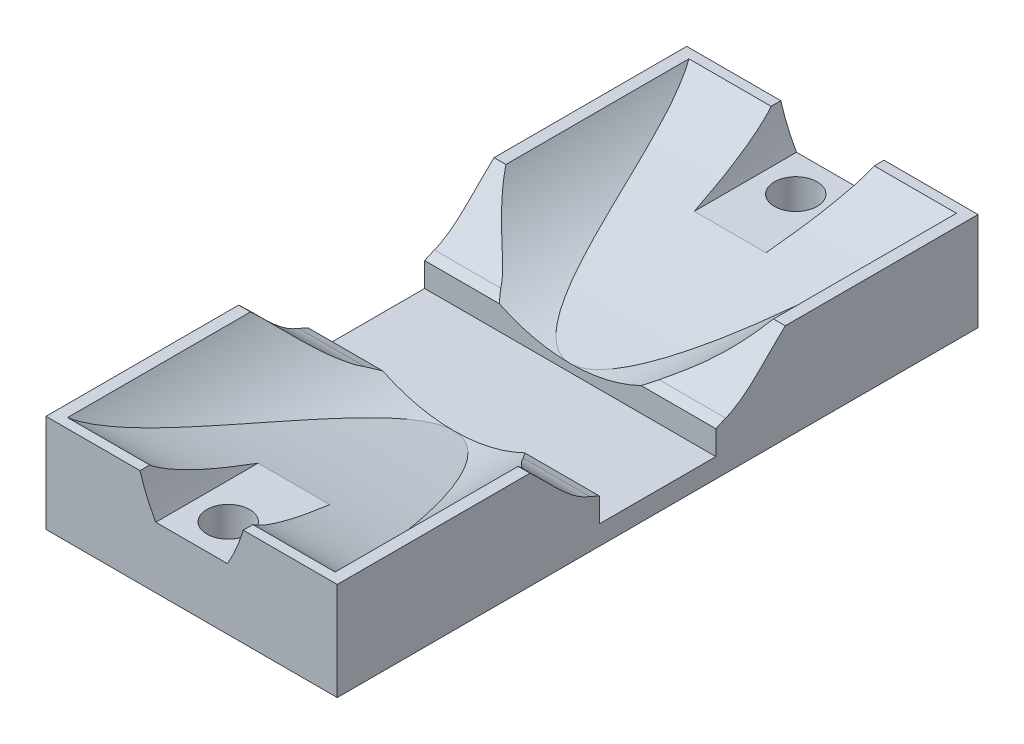
SolidWorks part; units mm, degrees
ref_plane "Front Plane" through (0, 0, 0) normal (0, 0, 1) x (1, 0, 0)
ref_plane "Top Plane" through (0, 0, 0) normal (0, 1, 0) x (1, 0, 0)
ref_plane "Right Plane" through (0, 0, 0) normal (1, 0, 0) x (0, 0, -1)
sketch "Sketch1" plane through (0, 0, 0) normal (0, 1, 0) x (1, 0, 0)
  line L0 (-185, -65) -> (5, -65)
  line L1 (-185, 135) -> (185, 135)
  line L2 (-185, 135) -> (-185, -65)
  line L4 (185, 135) -> (185, -135)
  line L8 (91.1823, -135) -> (185, -135)
  arc A0 (5, -65) -> (91.1823, -135) centre (5, -153.0528) cw
  point P0 (0, 0)
extrude "Boss-Extrude1" add sketch "Sketch1" along normal blind 15.0459
sketch "Sketch2" plane through (0, 15.0459, 0) normal (0, 1, 0) x (1, 0, 0)
  line L0 (-175, -35) -> (-175, 30)
  line L1 (-175, -35) -> (-142.5, -35)
  line L2 (-175, 125) -> (-142.5, 125)
  line L3 (-95, -35) -> (-95, 30)
  line L12 (-185, 135) -> (-185, -65) construction
  line L13 (-185, 135) -> (-142.5, 135)
  line L14 (-85, -45) -> (-85, 30)
  line L15 (-185, -45) -> (-142.5, -45)
  line L16 (-185, -45) -> (-185, 30)
  line L17 (-135, 196.4351) -> (-135, -108.7974) construction
  line L18 (-142.5, 135) -> (-142.5, 125)
  line L19 (-127.5, 135) -> (-127.5, 125)
  line L20 (-127.5, 135) -> (-85, 135)
  line L21 (-185, 135) -> (-85, 135) construction
  line L22 (-127.5, 125) -> (-95, 125)
  line L23 (-175, 125) -> (-95, 125) construction
  line L24 (-208.7616, 45) -> (-62.2564, 45) construction
  line L25 (-127.5, -45) -> (-127.5, -35)
  line L26 (-142.5, -45) -> (-142.5, -35)
  line L27 (-127.5, -35) -> (-95, -35)
  line L28 (-175, -35) -> (-95, -35) construction
  line L29 (-127.5, -45) -> (-85, -45)
  line L30 (-185, -45) -> (-85, -45) construction
  line L31 (185, 135) -> (-185, 135) construction
  line L32 (-175, 60) -> (-185, 60)
  line L33 (-175, 30) -> (-185, 30)
  line L34 (-95, 60) -> (-85, 60)
  line L35 (-95, 30) -> (-85, 30)
  line L36 (-175, 60) -> (-175, 125)
  line L37 (-175, -35) -> (-175, 125) construction
  line L38 (-185, 60) -> (-185, 135)
  line L39 (-185, -45) -> (-185, 135) construction
  line L40 (-85, 60) -> (-85, 135)
  line L41 (-85, -45) -> (-85, 135) construction
  line L42 (-95, 60) -> (-95, 125)
  line L43 (-95, -35) -> (-95, 125) construction
  point P14 (-135, 135.0621)
  point P18 (-175, 45)
  dimension "D1" = 160
  dimension "D2" = 80
  dimension "D3" = 10
  dimension "D4" = 7.5
  dimension "D5" = 50
  dimension "D6" = 30
  dimension "D7" = 15
extrude "Boss-Extrude2" add sketch "Sketch2" along normal blind 30
sketch "Sketch3" plane through (0, 0, -125) normal (0, 0, 1) x (1, 0, 0)
  line L0 (-127.5, 15.0459) -> (-142.5, 15.0459) construction
  line L4 (-142.5, 15.0459) -> (-142.5, 13.7784)
  line L7 (-142.5, 13.7784) -> (-127.5, 13.7784)
  line L8 (-175, 15.0459) -> (-142.5, 15.0459)
  line L9 (-142.5, 15.0459) -> (-142.5, 45.0459)
  line L10 (-142.5, 45.0459) -> (-175, 45.0459)
  line L11 (-175, 45.0459) -> (-175, 15.0459)
  line L12 (-175, 15.0459) -> (-142.5, 15.0459)
  line L14 (-142.5, 45.0459) -> (-175, 45.0459)
  line L15 (-175, 45.0459) -> (-175, 15.0459)
  line L16 (-127.5, 15.0459) -> (-95, 15.0459)
  line L17 (-95, 15.0459) -> (-95, 45.0459)
  line L18 (-95, 45.0459) -> (-127.5, 45.0459)
  line L19 (-127.5, 45.0459) -> (-127.5, 15.0459)
  line L20 (-127.5, 15.0459) -> (-95, 15.0459)
  line L21 (-95, 15.0459) -> (-95, 45.0459)
  line L22 (-95, 45.0459) -> (-127.5, 45.0459)
  line L24 (-127.5, 13.7784) -> (-127.5, 15.0459)
  line L27 (-142.5, 15.0459) -> (-142.5, 45.0459)
  line L28 (-127.5, 45.0459) -> (-127.5, 15.0459)
  arc A0 (-175, 45.0459) -> (-138.7313, 15.2133) centre (-135, 56.7125) ccw
  arc A1 (-131.2687, 15.2133) -> (-95, 45.0459) centre (-135, 56.7125) ccw
  arc A2 (-138.7313, 15.2133) -> (-131.2687, 15.2133) centre (-135, 56.7125) ccw
  point P0 (-135, 15.0459)
  line M9 (-175, 15.0459) -> (-142.5, 15.0459)
  line M10 (-142.5, 15.0459) -> (-142.5, 45.0459)
  line M12 (-175, 45.0459) -> (-175, 15.0459)
  dimension "D1" = 0
  dimension "D2" = 0
extrude "Boss-Extrude3" add sketch "Sketch3" along normal up to surface (160 mm away) contours A0 M12 M9 M10 | A0 L20 L21 | A0 M10 region at (-135, 14.539, -125) region at (-165.9764, 23.0143, -125) region at (-104.0236, 23.0143, -125) up to face at (-158.75, 30.0459, 35)
sketch "Sketch5" plane through (-185, 0, 0) normal (-1, 0, 0) x (0, 0, 1)
  line L0 (-60, 45.0459) -> (-30, 45.0459)
  line L10 (-135, 0) -> (65, 0)
  line L11 (65, 0) -> (65, 15.0459)
  line L12 (65, 15.0459) -> (45, 15.0459)
  line L13 (45, 15.0459) -> (45, 45.0459)
  line L14 (45, 45.0459) -> (-30, 45.0459)
  line L15 (-30, 45.0459) -> (-30, 15.0459)
  line L16 (-30, 15.0459) -> (-60, 15.0459)
  line L17 (-60, 15.0459) -> (-60, 45.0459)
  line L18 (-60, 45.0459) -> (-135, 45.0459)
  line L19 (-135, 45.0459) -> (-135, 0)
  line L25 (-30, 45.0459) -> (-30, 15.0459)
  line L26 (-30, 15.0459) -> (-60, 15.0459)
  line L27 (-60, 15.0459) -> (-60, 45.0459)
  dimension "D1" = 0
extrude "Cut-Extrude1" cut sketch "Sketch5" against normal through all both and the other way through all
sketch "Sketch6" plane through (0, 15.0459, 0) normal (0, 1, 0) x (1, 0, 0)
  line L0 (-85, 60) -> (-85, 30)
  line L1 (-200, -45) -> (-127.5, -45)
  line L18 (-85, 135) -> (-85, 60)
  line L19 (-85, 60) -> (-135, 60)
  line L21 (-185, 60) -> (-185, 30)
  line L22 (-185, 30) -> (-135, 30)
  line L24 (-85, 30) -> (-85, -45)
  line L25 (-85, 30) -> (-85, -45)
  line L26 (-85, -45) -> (-127.5, -45)
  line L27 (-85, -45) -> (-127.5, -45)
  line L28 (-135, 60) -> (-185, 60)
  line L29 (-135, 60) -> (-185, 60)
  line L30 (-135, 30) -> (-85, 30)
  line L31 (-185, -45) -> (-185, -65)
  line L32 (-185, -65) -> (5, -65)
  line L33 (91.1823, -135) -> (185, -135)
  line L34 (185, -135) -> (185, 135)
  line L35 (185, 135) -> (-85, 135)
  line L36 (-85, 135) -> (-85, 60)
  line L37 (-85, 60) -> (-135, 60)
  line L39 (-185, 60) -> (-185, 30)
  line L40 (-185, 30) -> (-135, 30)
  line L49 (-185, -45) -> (-185, -65)
  line L50 (-185, -65) -> (5, -65)
  line L51 (91.1823, -135) -> (185, -135)
  line L52 (185, -135) -> (185, 135)
  line L53 (185, 135) -> (-85, 135)
  line L54 (-135, 30) -> (-85, 30)
  line L55 (-127.5, -45) -> (-127.5, -35)
  line L56 (-127.5, -45) -> (-127.5, -35)
  line L57 (-127.5, -35) -> (-135, -35)
  line L58 (-127.5, -35) -> (-135, -35)
  line L59 (-135, -35) -> (-142.5, -35)
  line L60 (-135, -35) -> (-142.5, -35)
  line L61 (-142.5, -35) -> (-142.5, -45)
  line L62 (-142.5, -35) -> (-142.5, -45)
  line L63 (-142.5, -45) -> (-185, -45)
  line L64 (-142.5, -45) -> (-185, -45)
  arc A1 (91.1823, -135) -> (5, -65) centre (5, -153.0528) ccw
  arc A2 (91.1823, -135) -> (5, -65) centre (5, -153.0528) ccw
  line M20 (-85, 135) -> (-85, 60)
  line M26 (-85, 30) -> (-85, -45)
  line M27 (-85, -45) -> (-127.5, -45)
  line M32 (-142.5, -45) -> (-185, -45)
  line M33 (-185, -45) -> (-185, -65)
  line M34 (-185, -65) -> (5, -65)
  arc M35 (5, -65) -> (91.1823, -135) centre (5, -153.0528) cw
  line M36 (91.1823, -135) -> (185, -135)
  line M37 (185, -135) -> (185, 135)
  line M38 (185, 135) -> (-85, 135)
  dimension "D1" = 0
extrude "Cut-Extrude2" cut sketch "Sketch6" against normal blind 30 contours L1 L0 M32 M33 M34 M35 M36 M37 M38 M20 M26 M27 region at (53.7672, 15.0459, -15.5574)
sketch "Sketch8" plane through (0, 15.0459, 0) normal (0, 1, 0) x (1, 0, 0)
  line L6 (-135, 30) -> (-85, 30)
  line L7 (-85, 30) -> (-85, 60)
  line L8 (-85, 60) -> (-135, 60)
  line L9 (-135, 60) -> (-185, 60)
  line L10 (-185, 60) -> (-185, 30)
  line L11 (-135, 60) -> (-185, 60)
  line L12 (-135, 30) -> (-85, 30)
  line L13 (-85, 30) -> (-85, 60)
  line L14 (-85, 60) -> (-135, 60)
  line L16 (-185, 60) -> (-185, 30)
  line L18 (-185, 30) -> (-135, 30)
  line L19 (-185, 30) -> (-135, 30)
  dimension "D1" = 0
extrude "Cut-Extrude3" cut sketch "Sketch8" against normal blind 2.0105
sketch "Sketch9" plane through (0, 0, 45) normal (0, 0, 1) x (1, 0, 0)
  line L0 (-142.5, 45.0459) -> (-142.5, 15.0459) construction
  line L1 (-127.5, 45.0459) -> (-142.5, 45.0459)
  line L2 (-135, 51.2467) -> (-135, 10.8591) construction
  line L4 (-150, 45.0459) -> (-120, 45.0459)
  line L5 (-144.2328, 23.7882) -> (-125.7672, 23.7882)
  arc A0 (-150, 45.0459) -> (-144.2328, 23.7882) centre (-106.9594, 45.3116) ccw
  arc A1 (-120, 45.0459) -> (-125.7672, 23.7882) centre (-163.0406, 45.3116) cw
  point P5 (-135, 45.0459)
  dimension "D1" = 30
ref_plane "Plane1" through (0, 0, -45) normal (0, 0, 1) x (1, 0, 0)
ref_plane "Plane2" through (-135, 0, 0) normal (1, 0, 0) x (0, 0, -1)
sketch "Sketch11" plane through (0, 0, 45) normal (0, 0, 1) x (1, 0, 0)
  line L0 (-127.5, 45.0459) -> (-142.5, 45.0459) construction
  line L1 (-127.5, 45.0459) -> (-142.5, 45.0459)
  line L2 (-120, 45.0459) -> (-150, 45.0459)
  line L3 (-144.2328, 23.7882) -> (-125.7672, 23.7882)
  line L4 (-120, 45.0459) -> (-150, 45.0459)
  line L5 (-144.2328, 23.7882) -> (-125.7672, 23.7882)
  arc A2 (-125.7672, 23.7882) -> (-120, 45.0459) centre (-163.0406, 45.3116) ccw
  arc A3 (-150, 45.0459) -> (-144.2328, 23.7882) centre (-106.9594, 45.3116) ccw
  arc A4 (-125.7672, 23.7882) -> (-120, 45.0459) centre (-163.0406, 45.3116) ccw
  arc A5 (-150, 45.0459) -> (-144.2328, 23.7882) centre (-106.9594, 45.3116) ccw
  dimension "D1" = 0
sketch "Sketch12" plane through (-135, 0, 0) normal (1, 0, 0) x (0, 0, -1)
  line L0 (-35, 33.2724) -> (-35, 15.0079)
  line L1 (-35, 45.0459) -> (-35, 15.7264) construction
  line L2 (-35, 15.0079) -> (30, 15.0459)
  line L3 (30, 15.0459) -> (30, 45.0459) construction
  line L4 (30, 45.0459) -> (30, 13.0354) construction
  line L6 (-35, 33.2724) -> (-23.6227, 24.4577) construction
  line L7 (-23.6227, 24.4577) -> (30, 15.0459) construction
  spline S0 degree 2 poles (-35, 33.2724) (-23.6227, 24.4577) (30, 15.0459) knots 0 0 0 1 1 1
extrude "Boss-Extrude6" add sketch "Sketch12" along normal up to next and the other way up to surface other way up to face at (-185, 25.7818, -45)
sketch "Sketch13" plane through (0, 0, 45) normal (0, 0, 1) x (1, 0, 0)
  line L0 (-142.5, 45.0459) -> (-127.5, 45.0459)
  line L8 (-185, 45.0459) -> (-185, 0)
  line L9 (-185, 0) -> (-85, 0)
  line L10 (-85, 0) -> (-85, 45.0459)
  line L11 (-85, 45.0459) -> (-127.5, 45.0459)
  line L12 (-127.5, 45.0459) -> (-127.5, 15.0459)
  line L13 (-127.5, 15.0459) -> (-142.5, 15.0459)
  line L14 (-142.5, 15.0459) -> (-142.5, 45.0459)
  line L15 (-142.5, 45.0459) -> (-185, 45.0459)
  line L20 (-127.5, 45.0459) -> (-127.5, 15.0459)
  line L21 (-127.5, 15.0459) -> (-142.5, 15.0459)
  line L22 (-142.5, 15.0459) -> (-142.5, 45.0459)
  dimension "D1" = 0
extrude "Boss-Extrude7" add sketch "Sketch13" against normal up to surface (10 mm away) up to face at (-157.4777, 39.1046, 35)
sketch "Sketch14" plane through (0, 0, -135) normal (0, 0, -1) x (-1, 0, 0)
  line L0 (142.5, 45.0459) -> (127.5, 45.0459)
  line L8 (85, 45.0459) -> (85, 0)
  line L9 (85, 0) -> (185, 0)
  line L10 (185, 0) -> (185, 45.0459)
  line L11 (185, 45.0459) -> (142.5, 45.0459)
  line L12 (142.5, 45.0459) -> (142.5, 15.0459)
  line L13 (142.5, 15.0459) -> (127.5, 15.0459)
  line L14 (127.5, 15.0459) -> (127.5, 45.0459)
  line L15 (127.5, 45.0459) -> (85, 45.0459)
  line L20 (142.5, 45.0459) -> (142.5, 15.0459)
  line L21 (142.5, 15.0459) -> (127.5, 15.0459)
  line L22 (127.5, 15.0459) -> (127.5, 45.0459)
  dimension "D1" = 0
extrude "Boss-Extrude8" add sketch "Sketch14" against normal up to surface (10 mm away) up to face at (-154.72, 33.7356, -125)
mirror "Mirror3" about plane through (0, 0, -45) normal (0, 0, 1) of "Boss-Extrude6"
extrude "Cut-Extrude6" cut sketch "Sketch9" against normal blind 192 contours A0 L5 A1 L4
sketch "Sketch18" plane through (0, 0, 0) normal (0, -1, 0) x (1, 0, 0)
  line L1 (-135, 11.1736) -> (-135, 57.7469) construction
  line L2 (-125.7672, 11.1736) -> (-144.2328, 11.1736) construction
  circle A0 centre (-135, 28.0736) radius 3
  dimension "D1" = 6
  dimension "D2" = 16.9
extrude "Cut-Extrude7" cut sketch "Sketch18" against normal blind 192
ref_plane "Plane3" through (0, 16, 0) normal (0, -1, 0) x (-1, 0, 0)
sketch "Sketch19" plane through (0, 16, 0) normal (0, -1, 0) x (-1, 0, 0)
  circle A0 centre (135, -28.0736) radius 5.5
  dimension "D1" = 11
extrude "Cut-Extrude8" cut sketch "Sketch19" against normal up to next
mirror "Mirror4" about plane through (0, 0, -45) normal (0, 0, 1) of "Cut-Extrude7", "Cut-Extrude8"
fillet "Fillet2" radius 2.5 6 edges at (-185, 29.0406, -30) (-85, 29.0406, -30) (-85, 29.0406, -60) (-185, 29.0406, -60) (-85, 13.0354, -45) (-185, 13.0354, -45)
sketch "Sketch20" plane through (-185, 0, 0) normal (-1, 0, 0) x (0, 0, 1)
  line L0 (-135, 45.0459) -> (-62.5, 45.0459) construction
  line L1 (-98.75, 45.0459) -> (-78.8485, 38.8047) construction
  line L2 (-78.8485, 38.8047) -> (-75.1777, 29.6534) construction
  line L4 (-62.5, 10.5354) -> (-62.5, 45.0459) construction
  line L5 (-75.1777, 29.6534) -> (-68.0945, 22.4152) construction
  line L6 (-68.0945, 22.4152) -> (-62.5, 20.3791) construction
  line L7 (-98.75, 45.0459) -> (-94.0749, 48.5989)
  line L8 (-94.0749, 48.5989) -> (-55.486, 48.5989)
  line L9 (-55.486, 48.5989) -> (-55.486, 27.9919)
  line L10 (-55.486, 27.9919) -> (-55.486, 17.229)
  line L11 (-55.486, 17.229) -> (-62.5, 20.3791)
  line L12 (-45, 70.5421) -> (-45, -15.4781) construction
  line L13 (8.75, 45.0459) -> (-11.1515, 38.8047) construction
  line L14 (-11.1515, 38.8047) -> (-14.8223, 29.6534) construction
  line L15 (-14.8223, 29.6534) -> (-21.9055, 22.4152) construction
  line L16 (-21.9055, 22.4152) -> (-27.5, 20.3791) construction
  line L17 (-34.514, 17.229) -> (-27.5, 20.3791)
  line L18 (-34.514, 27.9919) -> (-34.514, 17.229)
  line L19 (-34.514, 48.5989) -> (-34.514, 27.9919)
  line L20 (4.0749, 48.5989) -> (-34.514, 48.5989)
  line L21 (8.75, 45.0459) -> (4.0749, 48.5989)
  spline S0 degree 4 poles (-98.75, 45.0459) (-78.8485, 38.8047) (-75.1777, 29.6534) (-68.0945, 22.4152) (-62.5, 20.3791) knots 0 0 0 0 0 1 1 1 1 1
  spline S1 degree 4 poles (8.75, 45.0459) (-11.1515, 38.8047) (-14.8223, 29.6534) (-21.9055, 22.4152) (-27.5, 20.3791) knots 0 0 0 0 0 1 1 1 1 1
extrude "Cut-Extrude9" cut sketch "Sketch20" against normal blind 100
sketch "Sketch21" plane through (-185, 0, 0) normal (-1, 0, 0) x (0, 0, 1)
  line L0 (-135, 8.0354) -> (45, 8.0354)
  line L1 (45, 45.0459) -> (45, 0) construction
  line L2 (-135, 45.0459) -> (-135, 0) construction
  line L3 (-27.5, 10.5354) -> (-62.5, 10.5354) construction
  line L12 (-62.5, 10.5354) -> (-62.5, 20.3791)
  line L13 (-98.75, 45.0459) -> (-135, 45.0459)
  line L14 (-135, 45.0459) -> (-135, 0)
  line L15 (-135, 0) -> (45, 0)
  line L16 (45, 0) -> (45, 45.0459)
  line L17 (45, 45.0459) -> (8.75, 45.0459)
  line L18 (-27.5, 20.3791) -> (-27.5, 10.5354)
  line L19 (-27.5, 10.5354) -> (-62.5, 10.5354)
  line L22 (-135, 8.0354) -> (-135, 0)
  line L23 (-135, 0) -> (45, 0)
  line L24 (45, 0) -> (45, 8.0354)
  spline S2 degree 4 poles (-1025.1292, 291.1919) (949.7013, -51.9039) (-1032.6252, -87.7202) (861.4673, 219.062) (-1092.2514, -68.4609) knots -2.326781 -2.326781 -2.326781 -2.326781 -2.326781 2.690876 2.690876 2.690876 2.690876 2.690876 only from (-62.5, 20.3791) to (-98.75, 45.0459)
  spline S3 degree 4 poles (1002.2794, -68.465) (-951.4865, 219.0651) (942.6371, -87.7201) (-1039.7048, -51.9052) (935.1244, 291.191) knots -1.690894 -1.690894 -1.690894 -1.690894 -1.690894 3.326778 3.326778 3.326778 3.326778 3.326778 only from (8.75, 45.0459) to (-27.5, 20.3791)
  dimension "0.25" = 2.5
  dimension "D2" = 0
extrude "Cut-Extrude10" cut sketch "Sketch21" against normal up to next
ref_plane "Plane4" through (0, 55.0459, 0) normal (0, 1, 0) x (1, 0, 0)
sketch "Sketch23" plane through (0, 45.0459, 0) normal (0, 1, 0) x (1, 0, 0)
  line L0 (-120, -45) -> (-85, -45) construction
  line L1 (-92.5, 127.5) -> (-177.5, 127.5)
  line L2 (-92.5, 127.5) -> (-92.5, -37.5)
  line L3 (-92.5, -37.5) -> (-177.5, -37.5)
  line L4 (-177.5, 127.5) -> (-177.5, -37.5)
  line L5 (-185, -8.75) -> (-185, -45) construction
  line L6 (-85, 98.75) -> (-85, 135) construction
  line L7 (-85, 135) -> (-120, 135) construction
  line L9 (-85, 135) -> (-185, 135)
  line L10 (-85, 135) -> (-85, -45)
  line L11 (-85, -45) -> (-185, -45)
  line L12 (-185, 135) -> (-185, -45)
  dimension "D1" = 7.5
  dimension "D2" = 7.5
  dimension "D3" = 7.5
  dimension "D4" = 7.5
extrude "Cut-Extrude11" cut sketch "Sketch23" against normal up to next
sketch "Sketch24" plane through (-177.5, 0, 0) normal (-1, 0, 0) x (0, 0, 1)
  line L1 (-137.504, 52.717) -> (-81.3861, 52.717)
  line L2 (-137.504, 52.717) -> (-137.504, 39.5021)
  line L3 (-137.504, 39.5021) -> (-81.3861, 39.5021)
  line L4 (-81.3861, 52.717) -> (-81.3861, 39.5021)
ref_plane "Plane5" through (0, 33.2724, 0) normal (0, -1, 0) x (-1, 0, 0)
sketch "Sketch25" plane through (0, 33.2724, 0) normal (0, -1, 0) x (-1, 0, 0)
  line L1 (54.1094, 181.899) -> (212.6278, 181.899)
  line L2 (54.1094, 181.899) -> (54.1094, -75.5915)
  line L3 (54.1094, -75.5915) -> (212.6278, -75.5915)
  line L4 (212.6278, 181.899) -> (212.6278, -75.5915)
extrude "Cut-Extrude12" cut sketch "Sketch25" against normal blind 33
sketch "Sketch26" plane through (0, 33.2724, 0) normal (0, 1, 0) x (1, 0, 0)
  line L0 (-92.5, -37.5) -> (-92.5, 12.1191) construction
  line L1 (-97.5, -39.7498) -> (-172.5, -39.7498)
  line L2 (-97.5, -39.7498) -> (-97.5, 133.4128)
  line L3 (-97.5, 133.4128) -> (-172.5, 133.4128)
  line L4 (-172.5, -39.7498) -> (-172.5, 133.4128)
  line L5 (-78.4945, -53.5332) -> (-208.3728, -53.5332)
  line L6 (-78.4945, -53.5332) -> (-78.4945, 149.1556)
  line L7 (-78.4945, 149.1556) -> (-208.3728, 149.1556)
  line L8 (-208.3728, -53.5332) -> (-208.3728, 149.1556)
  line L9 (-177.5, 12.1191) -> (-177.5, -37.5) construction
  dimension "D1" = 5
  dimension "D2" = 5
extrude "Cut-Extrude13" cut sketch "Sketch26" against normal blind 33
